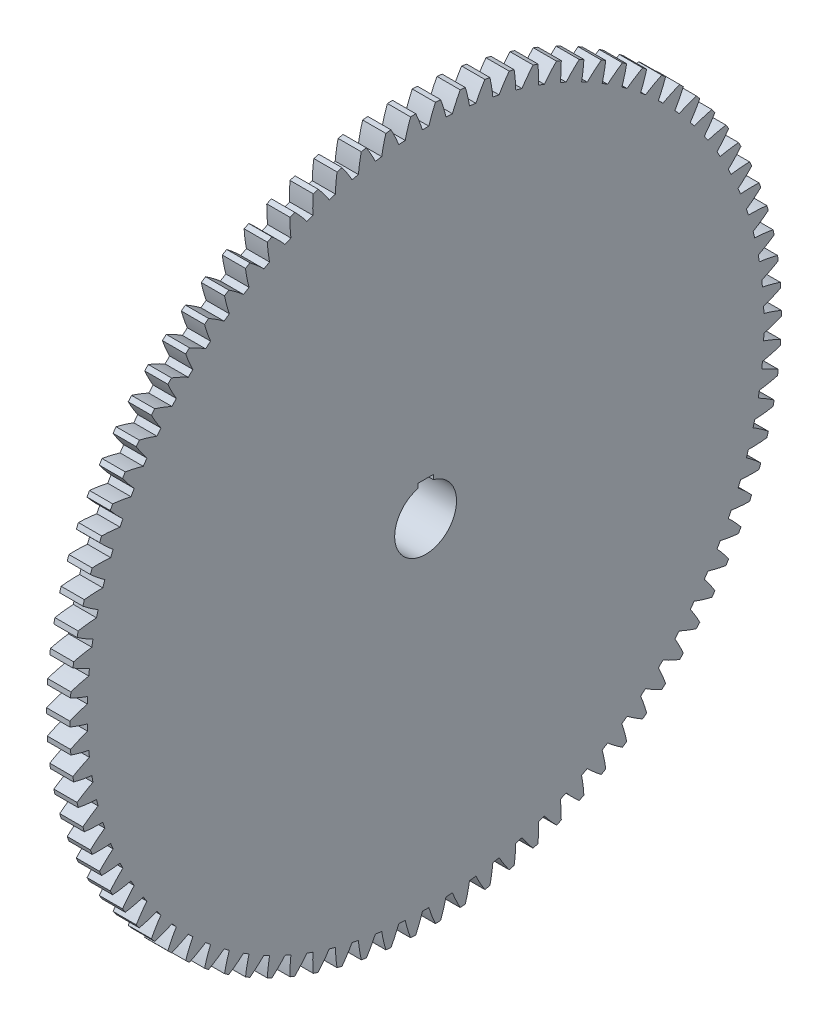
SolidWorks part; units mm, degrees
material "1023 Carbon Steel Sheet (SS)"
ref_plane "Plane1" through (0, 0, 0) normal (0, 0, 1) x (1, 0, 0)
ref_plane "Plane2" through (0, 0, 0) normal (0, 1, 0) x (1, 0, 0)
ref_plane "Plane3" through (0, 0, 0) normal (1, 0, 0) x (0, 0, -1)
sketch "HoldingSke" plane through (0, 0, 0) normal (0, 1, 0) x (1, 0, 0)
  line L0 (0, 0) -> (0, -0.04)
  line L1 (-15, 0) -> (100, 0) construction
  line L2 (0, 0) -> (-2.1039, 2.3779)
  line L3 (0, 0) -> (-11.863, 4.5341)
  line L4 (0, 0) -> (0, 8.636)
  line L5 (0, 0) -> (-140.5429, -52.4184)
  line L6 (0, 0) -> (-62.1722, -41.9478)
  line L7 (-2.1039, 2.3779) -> (30.1835, 148.8618)
  line L8 (-76.2, 54.61) -> (-64.8, 54.61)
  line L9 (-71.009, 38.7566) -> (-53.1078, 45.2721)
  line L10 (-76.2, 71.12) -> (104.1128, 71.12)
  line L11 (0, 0) -> (-75, 0)
  line L12 (-76.2, 101.6) -> (-75.26, 101.6)
  line L13 (24.9733, 27.94) -> (52.9518, 28.4284)
  line L14 (24.9733, 27.94) -> (24.9743, 27.94)
  line L15 (24.9733, 27.94) -> (100.4006, 29.5858)
  line L16 (-63.627, -25) -> (-12.827, -25)
  circle A0 centre (0, 0) radius 100
  circle A1 centre (0, 0) radius 375
  circle A2 centre (0, 0) radius 375
  circle A3 centre (0, 0) radius 100
  dimension "Num_teeth" = 90
  dimension "Pitch_radius" = 180.3128
  dimension "Width" = 75
  dimension "Thickness" = 75
sketch "BasProSke" plane through (0, 0, 0) normal (0, 1, 0) x (1, 0, 0)
  line L0 (-10, 0) -> (60, 0) construction
  line L1 (0, 0) -> (0, 1150)
  line L2 (0, 0) -> (75, 0)
  line L3 (75, 0) -> (75, 1150)
  line L4 (75, 1150) -> (0, 1150)
  dimension "Thickness" = 75
  dimension "Diameter" = 2300
revolve "Base-Revolve" add sketch "BasProSke" angle 360 about L0
sketch "TooCutSke" plane through (0, 0, 0) normal (1, 0, 0) x (0, 0, -1)
  line L1 (0, 0) -> (0, 107) construction
  line L2 (0, 0) -> (-21.2789, 1124.7987) construction
  line L3 (0, 0) -> (-78.5138, 2248.3419) construction
  line L4 (-21.2789, 1124.7987) -> (-39.2569, 1124.1709) construction
  arc A0 (10.4229, 1093.6993) -> (-10.4229, 1093.6993) centre (0, 0) ccw
  arc A1 (31.8283, 1149.5849) -> (-31.8283, 1149.5849) centre (0, 0) ccw
  circle A2 centre (0, 0) radius 1125 construction
  circle A3 centre (0, 0) radius 1057.1542 construction
  arc A4 (-10.4229, 1093.6993) -> (-31.8283, 1149.5849) centre (-440.4251, 961.0415) ccw
  arc A5 (31.8283, 1149.5849) -> (10.4229, 1093.6993) centre (440.4251, 961.0415) ccw
extrude "ToothCut" cut sketch "TooCutSke" along normal through all
fillet "Breaks" [suppressed] radius 0.5 tangent propagation no
fillet "RootFillets" [suppressed] radius 6.251
pattern_circular "TeethCuts" count 90 every 4 about axis through (-10, 0, 0) along (1, 0, 0) of "ToothCut", "RootFillets", "Breaks"
sketch "HubNeaOneSke" plane through (0, 0, 0) normal (-1, 0, 0) x (0, 0, 1)
  circle A0 centre (0, 0) radius 375
  dimension "Diameter" = 750
extrude "HubNearOne" add sketch "HubNeaOneSke" along normal blind 75.0001
sketch "HubNeaBotSke" plane through (0, 0, 0) normal (-1, 0, 0) x (0, 0, 1)
  circle A0 centre (0, 0) radius 375
  dimension "Diameter" = 750
extrude "HubNearBoth" [suppressed] add sketch "HubNeaBotSke" along normal blind 37.5
ref_plane "FarPln" through (75, 0, 0) normal (1, 0, 0) x (0, 0, -1)
sketch "HubFarSke" plane through (75, 0, 0) normal (1, 0, 0) x (0, 0, -1)
  circle A0 centre (0, 0) radius 375
  dimension "Diameter" = 750
extrude "HubFar" [suppressed] add sketch "HubFarSke" along normal blind 37.5
sketch "BorSke" plane through (0, 0, 0) normal (1, 0, 0) x (0, 0, -1)
  circle A0 centre (0, 0) radius 100
  dimension "Diameter" = 200
extrude "Bore" cut sketch "BorSke" along normal mid plane 300.0001
sketch "KeySke" plane through (0, 0, 0) normal (1, 0, 0) x (0, 0, -1)
  line L0 (-25, 0) -> (-25, 111.4)
  line L1 (-25, 111.4) -> (25, 111.4)
  line L2 (25, 111.4) -> (25, 0)
  line L3 (0, 0) -> (0, 34) construction
  line L4 (-25, 0) -> (25, 0)
  dimension "Width" = 50
extrude "Keyway" cut sketch "KeySke" along normal mid plane 300.0001
pattern_circular "Keyway2" [suppressed] count 2 every 90 about axis through (-10, 0, 0) along (1, 0, 0) reverse direction yes
equation "' \"Module@HoldingSke\" = 6.35"
equation "' \"Num_teeth@HoldingSke\" = 12"
equation "' \"Ap@HoldingSke\" =  20"
equation "' \"Ap@HoldingSke\" = 20"
equation "' \"Width@HoldingSke\" = 0.5 * 25.4"
equation "' \"Hub_dia@HoldingSke\"= 1 * 25.4"
equation "' \"Hub_dia@HoldingSke\" = 1 * 25.4"
equation "' \"Overall_len@HoldingSke\" = 1.0 * 25.4"
equation "' \"Bore@HoldingSke\" = 0.75 * 25.4"
equation "' \"T_dim@HoldingSke\" = 0.1 * 25.4"
equation "' \"Width@KeySke\" = 0.25 * 25.4"
equation "' \"Show_teeth@HoldingSke\" = 13"
equation "' \"Backlash@HoldingSke\" = 0.009 * 25.4"
equation "' \"Addendum_fac@HoldingSke\" = 1.0"
equation "' \"Dedendum_fac@HoldingSke\" = 1.25"
equation "' \"Dedendum_add@HoldingSke\" = 0.00005 * 25.4"
equation "' \"Clearance_fac@HoldingSke\" = 0.25"
equation "\"Pitch@HoldingSke\" = 1 / \"Module@HoldingSke\""
equation "\"Overcut_dia@TooCutSke\" = (\"Num_teeth@HoldingSke\" + 2 * \"Addendum_fac@HoldingSke\") / \"Pitch@HoldingSke\" + 0.002 * 25.4"
equation "\"Pitch_dia@TooCutSke\" = \"Num_teeth@HoldingSke\" / \"Pitch@HoldingSke\""
equation "\"Base_dia@TooCutSke\" = \"Num_teeth@HoldingSke\" / \"Pitch@HoldingSke\" * cos((\"Ap@HoldingSke\"  * 3.14159265 / 180))"
equation "\"Root_dia@TooCutSke\" = (\"Num_teeth@HoldingSke\" + 2) / \"Pitch@HoldingSke\" - 2 * (\"Addendum_fac@HoldingSke\" + \"Dedendum_fac@HoldingSke\") / \"Pitch@HoldingSke\" - \"Dedendum_add@HoldingSke\" * 2"
equation "\"Half_ang@TooCutSke\" = 180 / \"Num_teeth@HoldingSke\""
equation "\"Half_CT@TooCutSke\" = \"Num_teeth@HoldingSke\" / \"Pitch@HoldingSke\" * sin((3.14159265 / 2 / \"Num_teeth@HoldingSke\")) / 2 - 7 * \"Backlash@HoldingSke\" / 4"
equation "\"Flank_rad@TooCutSke\" = \"Num_teeth@HoldingSke\" / \"Pitch@HoldingSke\" / 5"
equation "\"Radius@RootFillets\" = \"Clearance_fac@HoldingSke\" / \"Pitch@HoldingSke\" + \"Dedendum_add@HoldingSke\""
equation "\"Break_rad@Breaks\" = 0.02 / \"Pitch@HoldingSke\""
equation "\"Thickness@HoldingSke\" = \"Width@HoldingSke\""
equation "\"OAL@HoldingSke\" = \"Thickness@HoldingSke\""
equation "\"MHD@HoldingSke\" = (\"Num_teeth@HoldingSke\" + 2) / \"Pitch@HoldingSke\" - 2 * (\"Addendum_fac@HoldingSke\" + \"Dedendum_fac@HoldingSke\")  / \"Pitch@HoldingSke\" - \"Dedendum_add@HoldingSke\" * 2"
equation "\"MBD@HoldingSke\" = (\"Num_teeth@HoldingSke\" + 2) / \"Pitch@HoldingSke\" - 2 * (\"Addendum_fac@HoldingSke\" + \"Dedendum_fac@HoldingSke\")  / \"Pitch@HoldingSke\" - \"Dedendum_add@HoldingSke\" * 2 - 0.002 * 25.4"
equation "\"MHD@HoldingSke\" = ((sgn( \"MHD@HoldingSke\" - \"Hub_dia@HoldingSke\" )-1)*( \"MHD@HoldingSke\" - \"Hub_dia@HoldingSke\" ))/-2+ \"Hub_dia@HoldingSke\""
equation "\"MBD@HoldingSke\" = ((sgn( \"MBD@HoldingSke\" - \"Bore@HoldingSke\" )-1)*( \"MBD@HoldingSke\" - \"Bore@HoldingSke\" ))/-2+ \"Bore@HoldingSke\""
equation "\"OAL@HoldingSke\" = ((sgn( \"OAL@HoldingSke\" - \"Overall_len@HoldingSke\" )+1)*( \"OAL@HoldingSke\" - \"Overall_len@HoldingSke\" ))/2 + \"Overall_len@HoldingSke\" + 0.000002 * 25.4"
equation "\"Num_teeth@TeethCuts\" = int( \"Show_teeth@HoldingSke\" ) + 1"
equation "\"Num_teeth@TeethCuts\" = ((sgn( \"Num_teeth@TeethCuts\" - \"Num_teeth@HoldingSke\" )-1)*( \"Num_teeth@TeethCuts\" - \"Num_teeth@HoldingSke\" ))/-2+ \"Num_teeth@HoldingSke\""
equation "\"Num_teeth@TeethCuts\" = ((sgn( \"Num_teeth@TeethCuts\" - 2.0)+1)*( \"Num_teeth@TeethCuts\" - 2.0))/2 +2.0"
equation "\"Angle@TeethCuts\" = 360.0 / \"Num_teeth@HoldingSke\""
equation "\"Diameter@BasProSke\" = (\"Num_teeth@HoldingSke\" + 2 * \"Addendum_fac@HoldingSke\") / \"Pitch@HoldingSke\""
equation "\"Thickness@BasProSke\"  = \"Thickness@HoldingSke\""
equation "' \"Fillet_rad@BasProSke\" =  \"Thickness@HoldingSke\" * 0.05"
equation "' \"Fillet_rad@BasProSke\" = \"Thickness@HoldingSke\" * 0.05"
equation "\"MHD@HoldingSke\" = ((sgn( \"MHD@HoldingSke\" - \"Root_dia@TooCutSke\" )-1)*( \"MHD@HoldingSke\" - \"Root_dia@TooCutSke\" ))/-2+ \"Root_dia@TooCutSke\""
equation "\"Diameter@HubNeaOneSke\" = \"MHD@HoldingSke\""
equation "\"Length@HubNearOne\" = \"OAL@HoldingSke\" - \"Thickness@BasProSke\""
equation "\"Diameter@HubNeaBotSke\" = \"MHD@HoldingSke\""
equation "\"Length@HubNearBoth\" = ( \"OAL@HoldingSke\" - \"Thickness@BasProSke\" ) / 2.0"
equation "\"Thickness@FarPln\" = \"Thickness@BasProSke\""
equation "\"Diameter@HubFarSke\" = \"MHD@HoldingSke\""
equation "\"Length@HubFar\" = ( \"OAL@HoldingSke\" - \"Thickness@BasProSke\" ) / 2.0"
equation "\"Diameter@BorSke\" = \"MBD@HoldingSke\""
equation "\"D1@Bore\" = \"OAL@HoldingSke\" * 2.0"
equation "\"D1@Keyway\" = \"OAL@HoldingSke\" * 2.0"
equation "\"Offset@KeySke\" = \"T_dim@HoldingSke\" + \"MBD@HoldingSke\" / 2.0"
